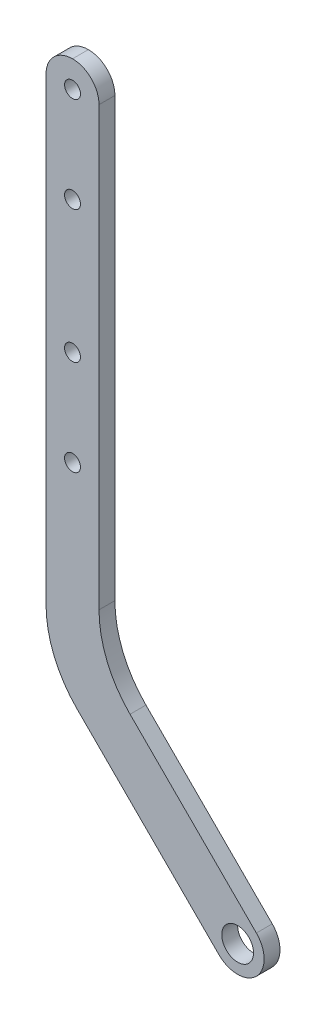
SolidWorks part; units mm, degrees
material "A-玻璃纤维"
ref_plane "前视基准面" through (0, 0, 0) normal (0, 0, 1) x (1, 0, 0)
ref_plane "上视基准面" through (0, 0, 0) normal (0, 1, 0) x (1, 0, 0)
ref_plane "右视基准面" through (0, 0, 0) normal (1, 0, 0) x (0, 0, -1)
sketch "草图1" plane through (0, 0, 0) normal (0, 0, 1) x (1, 0, 0)
  line L0 (0, 0) -> (0, 100)
  line L1 (0, 100) -> (10, 100)
  line L2 (10, 100) -> (10, 4.1421)
  line L3 (10, 4.1421) -> (43.2354, -29.0932)
  line L4 (43.2354, -29.0932) -> (36.1643, -36.1643)
  line L5 (0, 0) -> (36.1643, -36.1643)
  line L6 (5, 100) -> (5, 2.3794) construction
  line L7 (39.6998, -32.6288) -> (29.1758, -22.1048) construction
  line L8 (0, 0) -> (-4.5, 0) construction
  circle A0 centre (5, 34) radius 1.5
  circle A1 centre (36.1643, -29.0932) radius 3
  circle A2 centre (5, 52) radius 1.5
  circle A3 centre (5, 77) radius 1.5
  circle A4 centre (5, 95) radius 1.5
  point P11 (-4.5, 0)
  point P23 (5, 82.8977)
  dimension "D3" = 3
  dimension "D5" = 6
  dimension "D11" = 18
  dimension "D1" = 10
  dimension "D2" = 10
  dimension "D4" = 9.5
  dimension "D6" = 5
  dimension "D7" = 50
  dimension "D8" = 135
  dimension "D9" = 100
  dimension "D10" = 34
  dimension "D12" = 25
  dimension "D13" = 18
extrude "凸台-拉伸1" add sketch "草图1" along normal blind 3
fillet "圆角1" radius 20 2 edges at (0, 0, 1.5) (10, 4.1421, 1.5)
fillet "圆角2" radius 5 2 edges at (36.1643, -36.1643, 1.5) (43.2354, -29.0932, 1.5)
fillet "圆角3" radius 5 2 edges at (0, 100, 1.5) (10, 100, 1.5)
